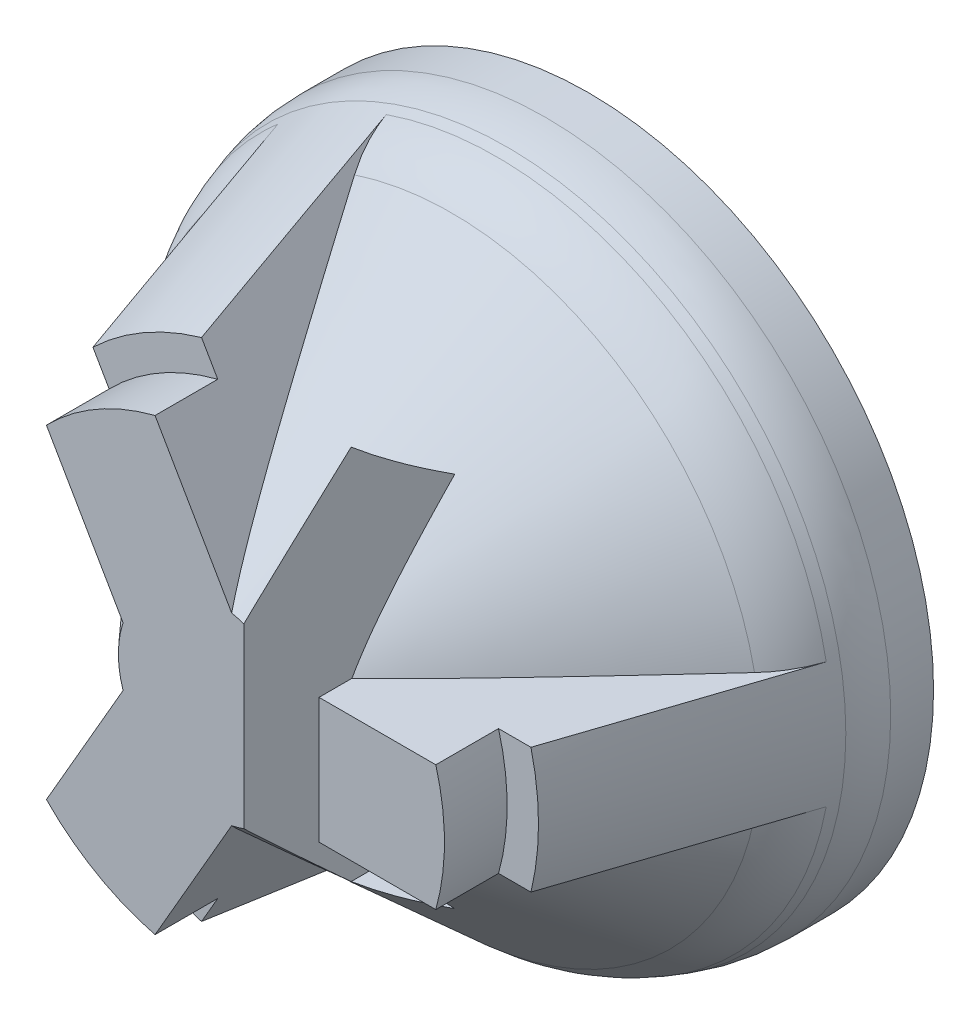
SolidWorks part; units mm, degrees
ref_plane "Plan de face" through (0, 0, 0) normal (0, 0, 1) x (1, 0, 0)
ref_plane "Plan de dessus" through (0, 0, 0) normal (0, 1, 0) x (1, 0, 0)
ref_plane "Plan de droite" through (0, 0, 0) normal (1, 0, 0) x (0, 0, -1)
sketch "Esquisse1" plane through (0, 0, 0) normal (0, 0, 1) x (1, 0, 0)
  line L0 (0, 0) -> (12, 0) construction
  line L1 (0, 0) -> (-6, 10.3923) construction
  line L2 (0, 0) -> (-6, -10.3923) construction
  line L3 (11.8322, 2) -> (2.2361, 2)
  line L4 (11.8322, -2) -> (2.2361, -2)
  line L5 (-4.184, -11.247) -> (0.614, -2.9365)
  line L6 (-7.6481, -9.247) -> (-2.8501, -0.9365)
  line L7 (-7.6481, 9.247) -> (-2.8501, 0.9365)
  line L8 (-4.184, 11.247) -> (0.614, 2.9365)
  circle A0 centre (0, 0) radius 12 construction
  circle A1 centre (0, 0) radius 3 construction
  circle A2 centre (0, 0) radius 3 construction
  arc A3 (11.8322, 2) -> (11.8322, -2) centre (0, 0) cw
  arc A4 (2.2361, -2) -> (1.5, -2.5981) centre (0, 0) cw
  arc A5 (2.2361, 2) -> (1.5, 2.5981) centre (0, 0) ccw
  arc A6 (0.614, -2.9365) -> (1.5, -2.5981) centre (0, 0) ccw
  arc A7 (-4.184, -11.247) -> (-7.6481, -9.247) centre (0, 0) cw
  arc A8 (-2.8501, -0.9365) -> (-3, 0) centre (0, 0) cw
  arc A9 (-2.8501, 0.9365) -> (-3, 0) centre (0, 0) ccw
  arc A10 (-7.6481, 9.247) -> (-4.184, 11.247) centre (0, 0) cw
  arc A11 (0.614, 2.9365) -> (1.5, 2.5981) centre (0, 0) cw
  point P30 (0, 0)
  dimension "D1" = 24
  dimension "D2" = 6
  dimension "D3" = 6
  dimension "D4" = 120
  dimension "D5" = 4
  dimension "D6" = 3
extrude "Boss.-Extru.1" add sketch "Esquisse1" along normal blind 12 contours A11 L8 A10 L7 A9 A8 L6 A7 L5 A6 A4 L4 A3 L3 A5 region at (0, 0, 0)
sketch "Esquisse4" plane through (0, 0, 0) normal (0, 1, 0) x (1, 0, 0)
  line L0 (12, 0) -> (3, -12) construction
  line L1 (3, -12) -> (0, -12)
  line L2 (0.614, -12) -> (2.2361, -12) construction
  line L3 (0, -12) -> (0, 0)
  line L4 (0, 0) -> (12, 0) construction
  line L5 (12, 0) -> (11.8322, 0) construction
  line L6 (11.8322, -12) -> (2.2361, -12) construction
  line L9 (12, -12) -> (12, 0) construction
  line L10 (12, -2) -> (12, 0)
  line L11 (12, 0) -> (0, 0)
  line L12 (3, -12) -> (12, -2)
  dimension "D1" = 2
  dimension "3" = 3
revolve "Révolution1" add sketch "Esquisse4" angle 360 about L3
sketch "Esquisse5" plane through (0, 0, 0) normal (0, 0, -1) x (-1, 0, 0)
  circle A0 centre (0, 0) radius 10.2
  dimension "D1" = 20.4
extrude "Enlèv. mat.-Extru.1" cut sketch "Esquisse5" against normal blind 2.5
sketch "Esquisse6" plane through (0, 0, 0) normal (0, 1, 0) x (1, 0, 0)
  line L0 (11, 0) -> (15.4808, 0)
  line L1 (11, 0) -> (11, -2)
  line L2 (15.4808, 0) -> (15.4808, -12)
  line L3 (15.4808, -12) -> (7.88, -12)
  line L4 (7.88, -12) -> (11, 0) construction
  line L5 (11.8322, -2) -> (-4.184, -2) construction
  line L6 (0, 0) -> (0, -11.8612) construction
  line L7 (11, -2) -> (8.4, -10)
  line L8 (11.8322, -12) -> (2.2361, -12) construction
  line L9 (11.8322, -12) -> (2.2361, -12) construction
  line L11 (8.4, -10) -> (7.4, -10)
  line L12 (7.4, -10) -> (7.4, -12)
  line L13 (7.4, -12) -> (7.88, -12)
  line L14 (12, -12) -> (12, 0) construction
  line L15 (12, 0) -> (-12, 0) construction
  dimension "D1" = 1
  dimension "D2" = 1
  dimension "D3" = 2
  dimension "D4" = 7.4
revolve "Enlèvement de matière-Révolution1" cut sketch "Esquisse6" angle 360 about L6
fillet "Congé2" radius 4 4 edges at (5.2174, -9.0368, 3.7391) (-10.4348, 0, 3.7391) (5.2174, 9.0368, 3.7391) (-11, 0, 2)
sketch "Esquisse7" plane through (0, 0, 12) normal (0, 0, 1) x (1, 0, 0)
  line L0 (1, 6) -> (3.4, 6)
  line L1 (3.4, 6) -> (3.4, -6)
  line L2 (3.4, -6) -> (1, -6)
  line L3 (1, -6) -> (1, 6)
  line L4 (0, 0) -> (7.4, 0) construction
  arc A2 (7.1246, -2) -> (7.1246, 2) centre (0, 0) ccw construction
  dimension "D1" = 12
  dimension "D2" = 12
  dimension "D3" = 2.4
  dimension "D4" = 1
extrude "Enlèv. mat.-Extru.2" cut sketch "Esquisse7" against normal offset from surface (8.5 mm away) 1 up to face at (-10.2, 0, 2.5)
